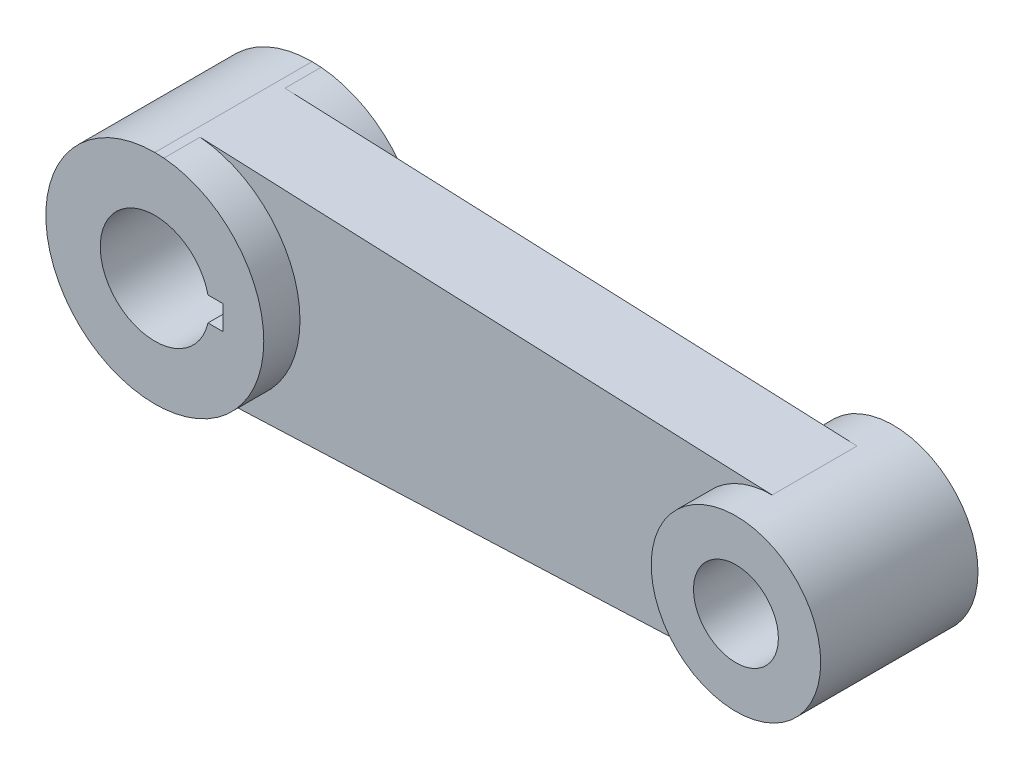
SolidWorks part; units mm, degrees
ref_plane "Front Plane" through (0, 0, 0) normal (0, 0, 1) x (1, 0, 0)
ref_plane "Top Plane" through (0, 0, 0) normal (0, 1, 0) x (1, 0, 0)
ref_plane "Right Plane" through (0, 0, 0) normal (1, 0, 0) x (0, 0, -1)
sketch "Sketch1" plane through (0, 0, 0) normal (0, 0, 1) x (1, 0, 0)
  line L0 (0, 14.2875) -> (76.2, 11.1125)
  line L1 (0, -14.2875) -> (76.2, -11.1125)
  circle A0 centre (0, 0) radius 14.2875
  circle A1 centre (0, 0) radius 7.1501
  circle A2 centre (76.2, 0) radius 11.1125
  circle A3 centre (76.2, 0) radius 5.5626
  dimension "D1" = 28.575
  dimension "D2" = 14.3002
  dimension "D3" = 11.1252
  dimension "D4" = 22.225
  dimension "D5" = 76.2
extrude "Boss-Extrude1" add sketch "Sketch1" along normal blind 4.7498 contours L0 A0 L1 A1 | A2 A3 region at (0.5775, 13.859, 0) region at (83.8355, 7.6355, 0)
extrude "Boss-Extrude2" add sketch "Sketch1<3>" against normal blind 11.1252 separate body contours A2 L0 A0 L1 region at (38.6092, 0, 0)
sketch "Sketch1<3>" plane through (0, 0, 0) normal (0, 0, 1) x (1, 0, 0) same geometry as "Sketch1"
extrude "Boss-Extrude3" add sketch "Sketch1<4>" against normal blind 15.875 contours A2 A3 | L0 A0 L1 A1 region at (0.5775, 13.859, 0) region at (83.8355, 7.6355, 0)
sketch "Sketch1<4>" plane through (0, 0, 0) normal (0, 0, 1) x (1, 0, 0) same geometry as "Sketch1"
sketch "Sketch2" plane through (0, 0, 0) normal (0, 0, 1) x (1, 0, 0)
  line L0 (0, 0) -> (13.9433, 0) construction
  line L1 (6.9716, 0) -> (6.9716, 1.5875)
  line L2 (6.9716, 0) -> (6.9716, -1.5875)
  line L3 (6.9716, 1.5875) -> (8.9274, 1.5875)
  line L4 (8.9274, 1.5875) -> (8.9274, -1.5875)
  line L5 (8.9274, -1.5875) -> (6.9716, -1.5875)
  circle A1 centre (0, 0) radius 7.1501 construction
  dimension "D1" = 1.5875
  dimension "D2" = 1.5875
  dimension "D3" = 1.9558
extrude "Cut-Extrude2" cut sketch "Sketch2" along normal blind 4.826 and the other way blind 4.6736
